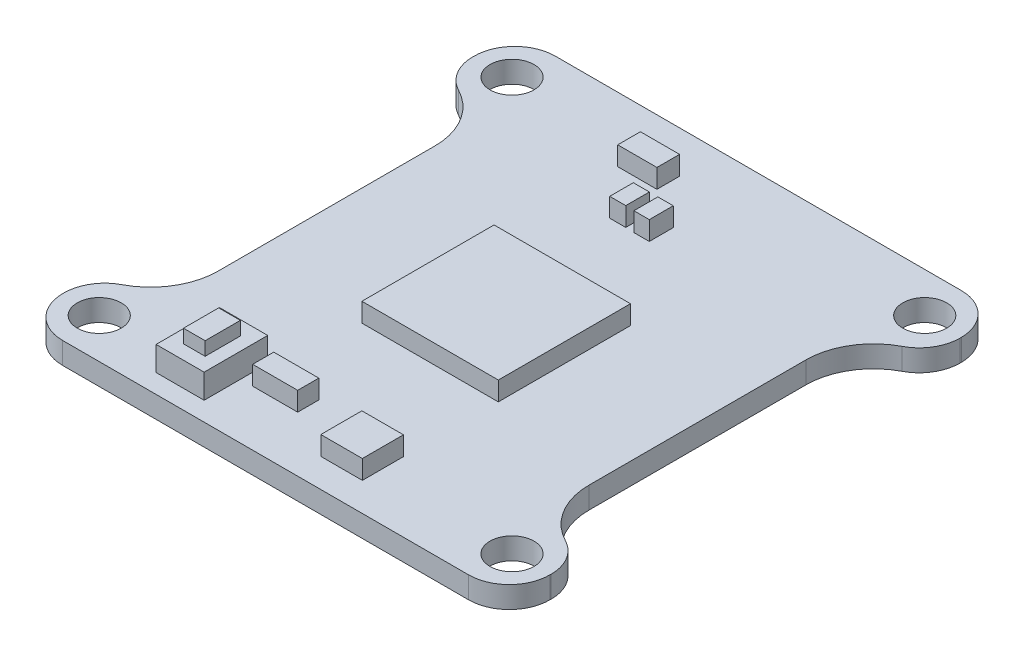
SolidWorks part; units mm, degrees
ref_plane "Front Plane" through (0, 0, 0) normal (0, 0, 1) x (1, 0, 0)
ref_plane "Top Plane" through (0, 0, 0) normal (0, 1, 0) x (1, 0, 0)
ref_plane "Right Plane" through (0, 0, 0) normal (1, 0, 0) x (0, 0, -1)
sketch "Sketch1" plane through (0, 0, 0) normal (0, 1, 0) x (1, 0, 0)
  line L0 (0, 18.2) -> (0, -18.2) construction
  line L1 (-18, 18.2) -> (18, 18.2)
  line L2 (-18, 18.2) -> (-18, -18.2)
  line L3 (-18, -18.2) -> (18, -18.2)
  line L4 (18, 18.2) -> (18, -18.2)
  line L5 (-18, 18.2) -> (18, -18.2) construction
  line L6 (-18, -18.2) -> (18, 18.2) construction
  line L7 (13.7, 18.2) -> (-13.7, 18.2)
  line L8 (13.7, 18.2) -> (13.7, -18.2)
  line L9 (13.7, -18.2) -> (-13.7, -18.2)
  line L10 (-13.7, 18.2) -> (-13.7, -18.2)
  line L11 (13.7, 18.2) -> (-13.7, -18.2) construction
  line L12 (13.7, -18.2) -> (-13.7, 18.2) construction
  line L13 (-18, 0) -> (18, 0) construction
  line L15 (18, 12.1) -> (-18, 12.1)
  line L16 (18, 12.1) -> (18, -12.1)
  line L17 (18, -12.1) -> (-18, -12.1)
  line L18 (-18, 12.1) -> (-18, -12.1)
  line L19 (18, 12.1) -> (-18, -12.1) construction
  line L20 (18, -12.1) -> (-18, 12.1) construction
  circle A0 centre (-15.25, 15.25) radius 1.625
  circle A1 centre (15.25, 15.25) radius 1.625
  circle A2 centre (15.25, -15.25) radius 1.625
  circle A3 centre (-15.25, -15.25) radius 1.625
  point P0 (0, 0)
  point P5 (0, 0)
  point P23 (0, 0)
  dimension "D4" = 3.25
  dimension "D1" = 36.4
  dimension "D2" = 36
  dimension "D3" = 27.4
  dimension "D5" = 30.5
  dimension "D6" = 30.5
  dimension "D7" = 24.2
extrude "PCB" add sketch "Sketch1" along normal blind 1.6 contours L15 L8 L1 L10 | L17 L8 L15 L10 | L4 L17 L8 L3 A2 | L8 L17 L10 L3 | L10 L17 L2 L3 A3 | L15 L4 L1 L8 A1 | L15 L10 L1 L2 A0 region at (-15.85, 0, -18.1254) region at (0, 0, -15.1499) region at (15.85, 0, -18.1254) region at (-15.85, 0, 12.1746) region at (0, 0, 0) region at (0, 0, 15.1499) region at (15.85, 0, 12.1746)
sketch "Sketch2" plane through (0, 1.6, 0) normal (0, 1, 0) x (1, 0, 0)
  line L1 (-5.0578, -6.0345) -> (5.023, -6.0345)
  line L2 (-5.0578, -6.0345) -> (-5.0578, 3.7323)
  line L3 (-5.0578, 3.7323) -> (5.023, 3.7323)
  line L4 (5.023, -6.0345) -> (5.023, 3.7323)
  line L5 (1.9534, -13.0458) -> (5.023, -13.0458)
  line L6 (1.9534, -13.0458) -> (1.9534, -16.0805)
  line L7 (1.9534, -16.0805) -> (5.023, -16.0805)
  line L8 (5.023, -13.0458) -> (5.023, -16.0805)
  line L9 (-5.616, 15.1038) -> (-2.7208, 15.1038)
  line L10 (-5.616, 15.1038) -> (-5.616, 13.4294)
  line L11 (-5.616, 13.4294) -> (-2.7208, 13.4294)
  line L12 (-2.7208, 15.1038) -> (-2.7208, 13.4294)
  line L13 (-2.6161, 11.5807) -> (-1.4301, 11.5807)
  line L14 (-2.6161, 11.5807) -> (-2.6161, 9.8366)
  line L15 (-2.6161, 9.8366) -> (-1.4301, 9.8366)
  line L16 (-1.4301, 11.5807) -> (-1.4301, 9.8366)
  line L17 (-0.8023, 11.5807) -> (0.3353, 11.5807)
  line L18 (-0.8023, 11.5807) -> (-0.8023, 9.8089)
  line L19 (-0.8023, 9.8089) -> (0.3353, 9.8089)
  line L20 (0.3353, 11.5807) -> (0.3353, 9.8089)
  line L21 (-1.7319, -12.5448) -> (-5.0578, -12.5448)
  line L22 (-1.7319, -12.5448) -> (-1.7319, -14.1049)
  line L23 (-1.7319, -14.1049) -> (-5.0578, -14.1049)
  line L24 (-5.0578, -12.5448) -> (-5.0578, -14.1049)
extrude "Top components" add sketch "Sketch2" along normal blind 1.4
fillet "Fillet1" radius 3 8 edges at (-18, 0.8, 12.1) (-18, 0.8, -12.1) (18, 0.8, -12.1) (18, 0.8, 12.1) (18, 0.8, 18.2) (-18, 0.8, 18.2) (-18, 0.8, -18.2) (18, 0.8, -18.2)
fillet "Fillet2" radius 5 4 edges at (13.7, 0.8, -12.1) (13.7, 0.8, 12.1) (-13.7, 0.8, 12.1) (-13.7, 0.8, -12.1)
sketch "Sketch3" plane through (0, 0, 0) normal (0, -1, 0) x (1, 0, 0)
  line L1 (-9.9064, -12.8365) -> (-6.7322, -12.8365)
  line L2 (-9.9064, -12.8365) -> (-9.9064, -15.8014)
  line L3 (-9.9064, -15.8014) -> (-6.7322, -15.8014)
  line L4 (-6.7322, -12.8365) -> (-6.7322, -15.8014)
  line L5 (-5.8601, -13.3597) -> (-2.7557, -13.3597)
  line L6 (-5.8601, -13.3597) -> (-5.8601, -14.8945)
  line L7 (-5.8601, -14.8945) -> (-2.7557, -14.8945)
  line L8 (-2.7557, -13.3597) -> (-2.7557, -14.8945)
  line L9 (2.1627, 10.325) -> (5.1625, 10.325)
  line L10 (2.1627, 10.325) -> (2.1627, 8.7553)
  line L11 (2.1627, 8.7553) -> (5.1625, 8.7553)
  line L12 (5.1625, 10.325) -> (5.1625, 8.7553)
  line L13 (-4.7788, 10.918) -> (-3.5231, 10.918)
  line L14 (-4.7788, 10.918) -> (-4.7788, 8.0228)
  line L15 (-4.7788, 8.0228) -> (-3.5231, 8.0228)
  line L16 (-3.5231, 10.918) -> (-3.5231, 8.0228)
  line L17 (-0.9767, -13.3597) -> (-2.1278, -13.3597)
  line L18 (-0.9767, -13.3597) -> (-0.9767, -15.4177)
  line L19 (-0.9767, -15.4177) -> (-2.1278, -15.4177)
  line L20 (-2.1278, -13.3597) -> (-2.1278, -15.4177)
extrude "Rear components" add sketch "Sketch3" along normal blind 1.4
sketch "Sketch4" plane through (0, 1.6, 0) normal (0, 1, 0) x (1, 0, 0)
  line L0 (-15, -18.2) -> (15, -18.2) construction
  line L1 (-9.5, -12.1) -> (-5.95, -12.1)
  line L2 (-9.5, -12.1) -> (-9.5, -16.8)
  line L3 (-9.5, -16.8) -> (-5.95, -16.8)
  line L4 (-5.95, -12.1) -> (-5.95, -16.8)
  dimension "D1" = 3.55
  dimension "D2" = 4.7
  dimension "D3" = 8.5
  dimension "D4" = 1.4
extrude "Button base" add sketch "Sketch4" along normal blind 1.8
sketch "Sketch5" plane through (0, 3.4, 0) normal (0, 1, 0) x (1, 0, 0)
  line L0 (-9.5, -12.1) -> (-5.95, -16.8) construction
  line L2 (-8.525, -13.15) -> (-6.925, -13.15)
  line L3 (-8.525, -13.15) -> (-8.525, -15.75)
  line L4 (-8.525, -15.75) -> (-6.925, -15.75)
  line L5 (-6.925, -13.15) -> (-6.925, -15.75)
  line L6 (-8.525, -13.15) -> (-6.925, -15.75) construction
  line L7 (-8.525, -15.75) -> (-6.925, -13.15) construction
  point P4 (-7.725, -14.45)
  dimension "D1" = 1.6
  dimension "D2" = 2.6
extrude "Button tip" add sketch "Sketch5" along normal blind 1
